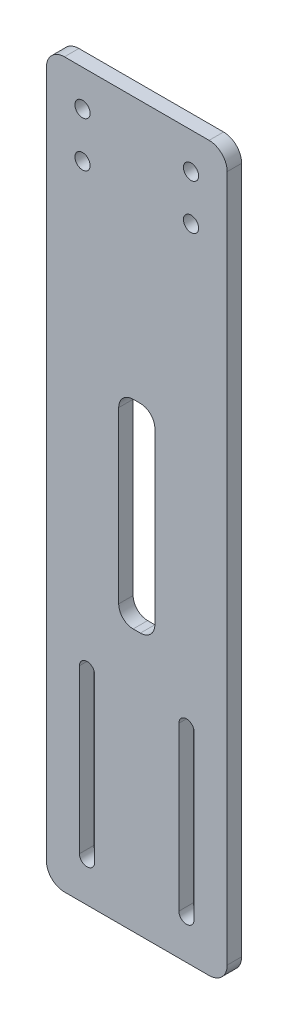
SolidWorks part; units mm, degrees
note: The reader was unsure of these and kept them because the rebuilt part matched: thickness of "Base-Flange1", "Sheet-Metal1".
ref_plane "Front Plane" through (0, 0, 0) normal (0, 0, 1) x (1, 0, 0)
ref_plane "Top Plane" through (0, 0, 0) normal (0, 1, 0) x (1, 0, 0)
ref_plane "Right Plane" through (0, 0, 0) normal (1, 0, 0) x (0, 0, -1)
sketch "Sketch1" plane through (0, 0, 0) normal (0, 0, 1) x (1, 0, 0)
  line L0 (-50, -177.5) -> (50, -177.5) construction
  line L1 (-40, 200) -> (40, 200)
  line L2 (-50, 190) -> (-50, -190)
  line L3 (-40, -200) -> (40, -200)
  line L4 (50, 190) -> (50, -190)
  line L5 (-50, 200) -> (50, -200) construction
  line L6 (-50, -200) -> (-27.9197, -111.679) construction
  line L7 (-50, -87.5) -> (50, -87.5) construction
  line L8 (-27.5, -87.5) -> (-27.5, -110) construction
  line L9 (27.5, -110) -> (27.5, -200) construction
  line L11 (23.3, -87.5) -> (23.3, -177.5)
  line L13 (31.7, -87.5) -> (31.7, -177.5)
  line L14 (-50, 180) -> (50, 180) construction
  line L15 (-50, 155) -> (50, 155) construction
  line L16 (-30, 200) -> (-30, 155) construction
  line L17 (30, 200) -> (30, 155) construction
  line L18 (-23.3, -177.5) -> (-23.3, -87.5)
  line L19 (-31.7, -87.5) -> (-31.7, -177.5)
  line L20 (-27.5, -110) -> (50, 200) construction
  line L21 (-27.5, -163.3) -> (-27.5, -200) construction
  line L23 (-2, -55) -> (2, -55)
  line L24 (-10, -47) -> (-10, 47)
  line L25 (-2, 55) -> (2, 55)
  line L26 (10, -47) -> (10, 47)
  line L27 (-10, -55) -> (10, 55) construction
  line L28 (-10, 55) -> (10, -55) construction
  arc A0 (40, -200) -> (50, -190) centre (40, -190) ccw
  arc A1 (-40, -200) -> (-50, -190) centre (-40, -190) cw
  arc A3 (23.3, -177.5) -> (31.7, -177.5) centre (27.5, -177.5) ccw
  arc A7 (31.7, -87.5) -> (23.3, -87.5) centre (27.5, -87.5) ccw
  arc A8 (50, 190) -> (40, 200) centre (40, 190) ccw
  arc A9 (-40, 200) -> (-50, 190) centre (-40, 190) ccw
  circle A11 centre (30, 180) radius 4.2
  circle A13 centre (30, 155) radius 4.2
  circle A14 centre (-30, 180) radius 4.2
  circle A15 centre (-30, 155) radius 4.2
  arc A17 (-31.7, -177.5) -> (-23.3, -177.5) centre (-27.5, -177.5) ccw
  arc A18 (-23.3, -87.5) -> (-31.7, -87.5) centre (-27.5, -87.5) ccw
  arc A19 (-2, -55) -> (-10, -47) centre (-2, -47) cw
  arc A20 (2, -55) -> (10, -47) centre (2, -47) ccw
  arc A21 (2, 55) -> (10, 47) centre (2, 47) cw
  arc A22 (-2, 55) -> (-10, 47) centre (-2, 47) ccw
  point P0 (0, 0)
  point P26 (0, 0)
  dimension "D3" = 10
  dimension "D8" = 10
  dimension "D13" = 20
  dimension "D15" = 8
  dimension "D1" = 100
  dimension "D2" = 400
  dimension "D4" = 22.5
  dimension "D5" = 90
  dimension "D6" = 22.5
  dimension "D7" = 22.5
  dimension "D9" = 20
  dimension "D10" = 25
  dimension "D11" = 20
  dimension "D12" = 20
  dimension "D14" = 110
  dimension "D16" = 8.4
  dimension "D17" = 8.4
base flange "Base-Flange1" sketch "Sketch1" thickness 8 reverse thickness direction no parameters "D1"=0.7366
sketch "Bend-Lines1" [suppressed] plane through (0, 0, 0) normal (0, 1, 0) x (1, 0, 0)
sketch "Bounding-Box1" [suppressed] plane through (0, 0, 0) normal (0, 1, 0) x (1, 0, 0)
sheet metal parameters "Sheet-Metal1" thickness 8 parameters "D1"=0.7366, "D7"=6
flat pattern "Flat-Pattern1" [suppressed]
sketch "Bend-Lines2" plane through (0, 0, 0) normal (0, 1, 0) x (1, 0, 0)
sketch3d "Bounding-Box2" [suppressed]
  line L0 (10, -10, 0) -> (10, 390, 0) construction
  line L1 (-90, -10, 0) -> (-90, 390, 0) construction
  line L2 (10, -10, 0) -> (-90, -10, 0) construction
  line L3 (10, 390, 0) -> (-90, 390, 0) construction
